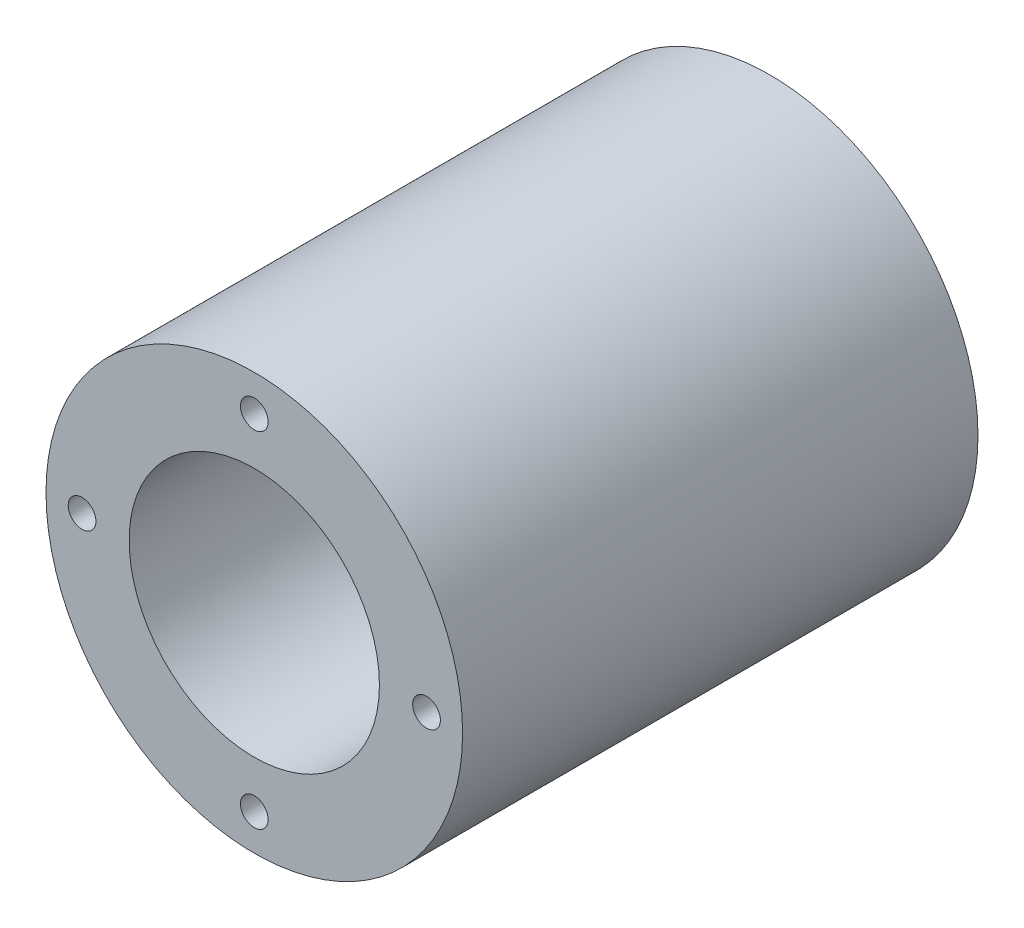
SolidWorks part; units mm, degrees
material "6061-T6 (SS)"
ref_plane "Front Plane" through (0, 0, 0) normal (0, 0, 1) x (1, 0, 0)
ref_plane "Top Plane" through (0, 0, 0) normal (0, 1, 0) x (1, 0, 0)
ref_plane "Right Plane" through (0, 0, 0) normal (1, 0, 0) x (0, 0, -1)
sketch "Sketch Spindle Skeleton" plane through (0, 0, 0) normal (1, 0, 0) x (0, 0, -1)
  line L0 (-95.847, -9.525) -> (-141.966, -9.525)
  line L5 (-1000, 0) -> (49000, 0)
  line L6 (0, -9.525) -> (0, 9.525)
  line L13 (0, 9.525) -> (-45.847, 9.525)
  line L26 (-45.847, 9.525) -> (-45.847, 12.7)
  line L27 (-45.847, 12.7) -> (-95.847, 12.7)
  line L32 (-95.847, 12.7) -> (-95.847, 9.525)
  line L34 (-160, 7) -> (-160, -7)
  line L36 (-95.847, -9.525) -> (-95.847, -12.7)
  line L37 (-95.847, -12.7) -> (-45.847, -12.7)
  line L38 (-45.847, -12.7) -> (-45.847, -9.525)
  line L39 (0, -9.525) -> (-45.847, -9.525)
  line L40 (-25.305, 37.6491) -> (-16.305, 37.6491)
  line L41 (-111.341, 22.6187) -> (-95.847, 22.6187)
  line L42 (-111.341, 22.6187) -> (-111.341, -22.6187)
  line L43 (-111.341, -22.6187) -> (-95.847, -22.6187)
  line L44 (-95.847, 22.6187) -> (-95.847, -22.6187)
  line L45 (-111.341, 22.6187) -> (-95.847, -22.6187) construction
  line L46 (-111.341, -22.6187) -> (-95.847, 22.6187) construction
  line L47 (-30.353, 22.6187) -> (-45.847, 22.6187)
  line L48 (-30.353, 22.6187) -> (-30.353, -22.6187)
  line L49 (-30.353, -22.6187) -> (-45.847, -22.6187)
  line L50 (-45.847, 22.6187) -> (-45.847, -22.6187)
  line L51 (-30.353, 22.6187) -> (-45.847, -22.6187) construction
  line L52 (-30.353, -22.6187) -> (-45.847, 22.6187) construction
  line L59 (-16.305, 37.6491) -> (-16.305, -37.6491)
  line L60 (-16.305, -37.6491) -> (-25.305, -37.6491)
  line L61 (-25.305, -22.6187) -> (-27.305, -22.6187)
  line L62 (-27.305, -22.6187) -> (-27.305, -12.5)
  line L63 (-27.305, -12.5) -> (-25.305, -12.5)
  line L64 (-25.305, -12.5) -> (-25.305, 12.5)
  line L65 (-25.305, 12.5) -> (-27.305, 12.5)
  line L66 (-27.305, 12.5) -> (-27.305, 22.6187)
  line L67 (-27.305, 22.6187) -> (-25.305, 22.6187)
  line L68 (-25.305, 22.6187) -> (-25.305, 37.6491)
  line L69 (-25.305, -22.6187) -> (-25.305, -37.6491)
  line L71 (-119.469, 37.6491) -> (-26.305, 37.6491)
  line L72 (-119.469, 37.6491) -> (-119.469, -37.6491)
  line L73 (-119.469, -37.6491) -> (-26.305, -37.6491)
  line L74 (-26.305, 37.6491) -> (-26.305, -37.6491)
  line L75 (-119.469, 37.6491) -> (-26.305, -37.6491) construction
  line L76 (-119.469, -37.6491) -> (-26.305, 37.6491) construction
  line L78 (-147.3, -7) -> (-160, -7)
  line L79 (-95.847, 9.525) -> (-141.966, 9.525)
  line L80 (-147.3, 7) -> (-160, 7)
  line L82 (-118.9065, 9.525) -> (-118.9065, -9.525) construction
  line L83 (-22.9235, 9.525) -> (-22.9235, -9.525) construction
  line L96 (-119.469, 37.6492) -> (-134.709, 37.6492)
  line L98 (-119.469, -37.6491) -> (-134.709, -37.6491)
  line L99 (-134.709, 37.6492) -> (-134.709, -37.6491)
  line L110 (-119.469, 37.6492) -> (-119.469, -37.6491)
  line L111 (-147.3, 7) -> (-147.3, 7.493)
  line L112 (-147.3, 7.493) -> (-141.966, 7.493)
  line L113 (-141.966, 7.493) -> (-141.966, 9.525)
  line L114 (-141.966, -9.525) -> (-141.966, -7.493)
  line L115 (-141.966, -7.493) -> (-147.3, -7.493)
  line L116 (-147.3, -7.493) -> (-147.3, -7)
  point P3 (0, 0)
  point P18 (-103.594, 0)
  point P24 (-38.1, 0)
  point P29 (-72.887, 0)
  point P48 (-16.305, 31.1339)
  point P70 (-134.709, 31.1339)
sketch "Sketch1" plane through (0, 0, 0) normal (1, 0, 0) x (0, 0, -1)
  line L0 (-26.305, 37.6491) -> (-26.305, -37.6491) construction
  line L1 (-119.469, -37.6491) -> (-26.305, -37.6491) construction
  line L2 (-119.469, 37.6491) -> (-119.469, -37.6491) construction
  line L3 (-119.469, 37.6491) -> (-26.305, 37.6491) construction
  line L4 (-26.305, 37.6491) -> (-26.305, -37.6491)
  line L5 (-119.469, -37.6491) -> (-26.305, -37.6491)
  line L6 (-119.469, 37.6491) -> (-119.469, -37.6491)
  line L7 (-119.469, 37.6491) -> (-26.305, 37.6491)
  line L9 (-30.353, 22.6187) -> (-45.847, 22.6187) construction
  line L10 (-119.469, 22.6187) -> (-26.305, 22.6187)
  line L15 (-119.469, 0) -> (-26.305, 0) construction
revolve "Revolve1" add sketch "Sketch1" angle 360 about L15 region at (0, 30.1339, 72.887)
sketch "Back Hole Top Location" plane through (0, 0, 26.305) normal (0, 0, -1) x (-1, 0, 0)
  point P9 (0, 31.1339)
hole_wizard "M6x1.0 Tapped Hole3" positions "Sketch8" profile "Sketch9" tap size "M6x1.0" standard "ANSI Metric"
sketch "Sketch8" plane through (0, 0, 26.305) normal (0, 0, -1) x (-1, 0, 0)
  point P0 (0, 31.1339)
sketch "Sketch9" plane through (0, 31.1339, 26.305) normal (1, 0, 0) x (0, 1, 0)
  line L0 (0, 0) -> (0, 16.5022)
  line L1 (0, 16.5022) -> (2.5, 15)
  line L2 (2.5, 15) -> (2.5, 0)
  line L5 (2.5, 0) -> (0, 0)
  line L10 (0, 16.5022) -> (-2.5, 15) construction
  line L11 (0, -6.35) -> (0, 107.95) construction
  dimension "Tap Drill Dia." = 5
  dimension "Tap Drill Depth" = 15
  dimension "Drill Angle" = 118
pattern_circular "BackFacePattern" count 6 over 360 about axis through (0, 0, 1000) along (0, 0, -1) of "M6x1.0 Tapped Hole3"
ref_plane "Midplane" through (0, 0, 72.887) normal (0, 0, -1) x (-1, 0, 0)
sketch "Front Hole Top Location" plane through (0, 0, 119.469) normal (0, 0, 1) x (1, 0, 0)
  point P0 (0, 31.1339)
hole_wizard "M6x1.0 Tapped Hole2" positions "Sketch5" profile "Sketch6" tap size "M6x1.0" standard "ANSI Metric"
sketch "Sketch5" plane through (0, 0, 119.469) normal (0, 0, 1) x (1, 0, 0)
  point P0 (0, 31.1339)
sketch "Sketch6" plane through (0, 31.1339, 119.469) normal (1, 0, 0) x (0, -1, 0)
  line L0 (0, 0) -> (0, 16.5022)
  line L1 (0, 16.5022) -> (2.5, 15)
  line L2 (2.5, 15) -> (2.5, 0)
  line L5 (2.5, 0) -> (0, 0)
  line L10 (0, 16.5022) -> (-2.5, 15) construction
  line L11 (0, -6.35) -> (0, 107.95) construction
  dimension "Tap Drill Dia." = 5
  dimension "Tap Drill Depth" = 15
  dimension "Drill Angle" = 118
pattern_circular "FrontFacePattern" count 4 over 360 about axis through (0, 0, 1000) along (0, 0, -1) of "M6x1.0 Tapped Hole2"
sketch "Sketch7" plane through (0, 0, 26.305) normal (0, 0, -1) x (-1, 0, 0)
  circle A0 centre (0, 0) radius 26.9875
  circle A1 centre (0, 0) radius 24.6062
  dimension "D1" = 53.975
  dimension "D2" = 49.2125
extrude "Cut-Extrude1" cut sketch "Sketch7" against normal blind 0.5
